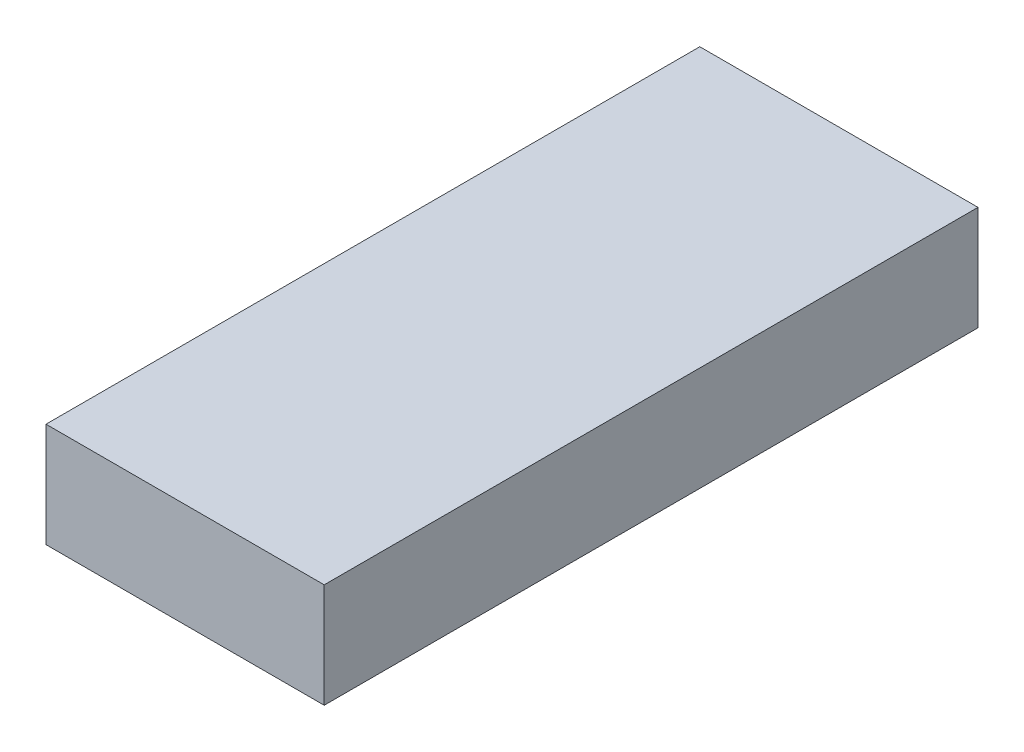
SolidWorks part; units mm, degrees
ref_plane "Front Plane" through (0, 0, 0) normal (0, 0, 1) x (1, 0, 0)
ref_plane "Top Plane" through (0, 0, 0) normal (0, 1, 0) x (1, 0, 0)
ref_plane "Right Plane" through (0, 0, 0) normal (1, 0, 0) x (0, 0, -1)
sketch "Sketch2" plane through (0, 0, 0) normal (0, 1, 0) x (1, 0, 0)
  line L1 (-12.7, 29.845) -> (12.7, 29.845)
  line L2 (-12.7, 29.845) -> (-12.7, -29.845)
  line L3 (-12.7, -29.845) -> (12.7, -29.845)
  line L4 (12.7, 29.845) -> (12.7, -29.845)
  line L5 (-12.7, 29.845) -> (12.7, -29.845) construction
  line L6 (-12.7, -29.845) -> (12.7, 29.845) construction
  point P0 (0, 0)
  dimension "D1" = 25.4
  dimension "D2" = 59.69
extrude "Boss-Extrude1" add sketch "Sketch2" along normal blind 9.525 contours L2 L3 L4 L1
